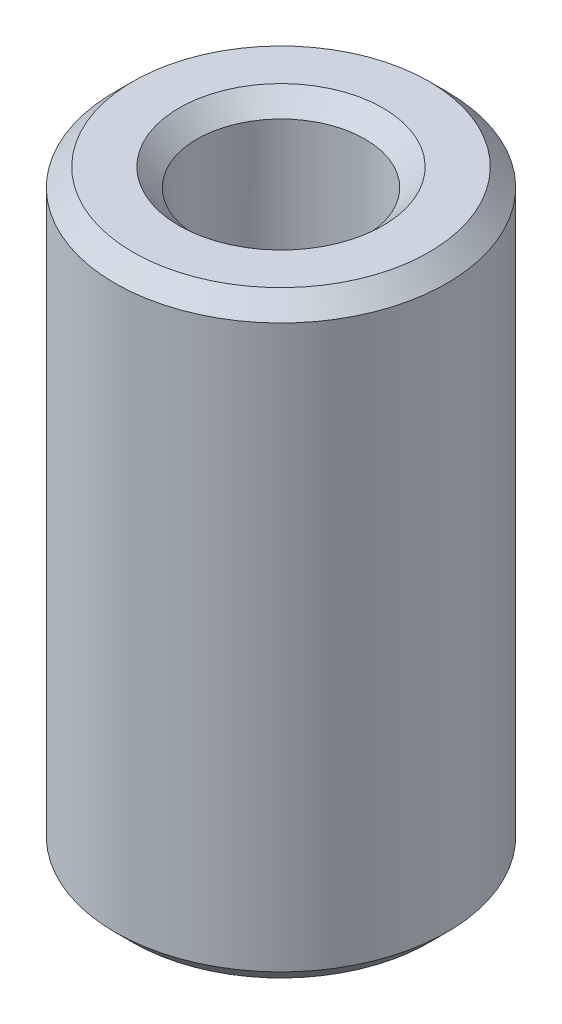
SolidWorks part; units mm, degrees
ref_plane "Front Plane" through (0, 0, 0) normal (0, 0, 1) x (1, 0, 0)
ref_plane "Top Plane" through (0, 0, 0) normal (0, 1, 0) x (1, 0, 0)
ref_plane "Right Plane" through (0, 0, 0) normal (1, 0, 0) x (0, 0, -1)
sketch "Sketch1" plane through (0, 0, 0) normal (0, 1, 0) x (1, 0, 0)
  circle A0 centre (0, 0) radius 12.5
  dimension "SLEEVE_OD" = 25
extrude "Boss-Extrude1" add sketch "Sketch1" along normal blind 45.0361
sketch "Sketch2" plane through (0, 0, 0) normal (0, 1, 0) x (1, 0, 0)
  circle A0 centre (0, 0) radius 6.3273
  dimension "BORE_D" = 12.6547
extrude "Cut-Extrude1" cut sketch "Sketch2" along normal through all
chamfer "Chamfer1" distance 1.3522 angle 45 4 edges at (0, 45.0361, 6.3273) (0, 0, 6.3273) (0, 0, 12.5) (0, 45.0361, 12.5)
